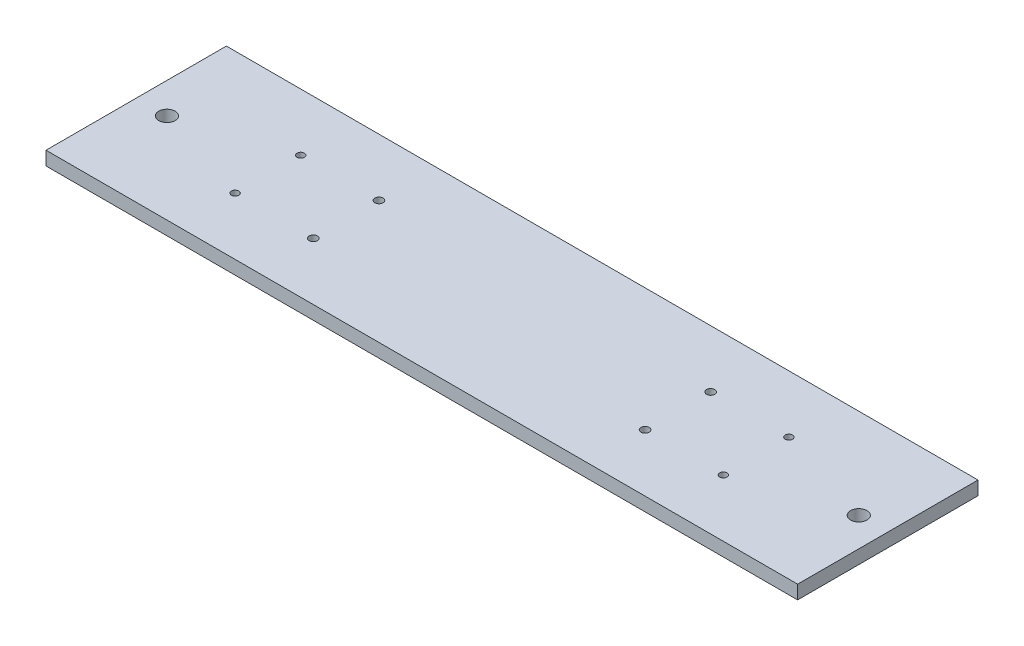
SolidWorks part; units mm, degrees
ref_plane "Front Plane" through (0, 0, 0) normal (0, 0, 1) x (1, 0, 0)
ref_plane "Top Plane" through (0, 0, 0) normal (0, 1, 0) x (1, 0, 0)
ref_plane "Right Plane" through (0, 0, 0) normal (1, 0, 0) x (0, 0, -1)
sketch "Sketch1" plane through (0, 0, 0) normal (0, 1, 0) x (1, 0, 0)
  line L0 (0, 111.2096) -> (0, -156.1617) construction
  line L2 (-275, -36) -> (-275, 36)
  line L6 (275, -36) -> (275, 36)
  line L9 (-275, -36) -> (275, -36)
  line L10 (-275, 36) -> (275, 36)
  circle A0 centre (-178.63, 24) radius 2.7
  circle A16 centre (-121.37, 24) radius 3.0274
  circle A23 centre (-178.63, -24) radius 2.7
  circle A24 centre (-121.37, -24) radius 3.0274
  circle A25 centre (121.37, 24) radius 3.0274
  circle A26 centre (121.37, -24) radius 3.0274
  circle A27 centre (178.63, -24) radius 2.7
  circle A28 centre (178.63, 24) radius 2.7
  circle A29 centre (-252.5, 0) radius 6
  circle A31 centre (253.76, 0) radius 6
  point P0 (0, 0)
  dimension "D4" = 178.63
  dimension "D5" = 5.4
  dimension "D7" = 22.5
  dimension "D3" = 275
  dimension "D2" = 550
  dimension "D1" = 57.26
  dimension "D6" = 12
  dimension "D8" = 21.24
extrude "Boss-Extrude1" add sketch "Sketch1" along normal blind 10
sketch "Sketch2" plane through (0, 0, -36) normal (0, 0, -1) x (-1, 0, 0)
  line L1 (-275, 10) -> (275, 10)
  line L2 (-275, 10) -> (-275, 0)
  line L3 (-275, 0) -> (275, 0)
  line L4 (275, 10) -> (275, 0)
extrude "Boss-Extrude2" add sketch "Sketch2" along normal blind 30
mirror "Mirror1" about plane through (0, 0, 0) normal (0, 0, 1) of "Boss-Extrude2"
